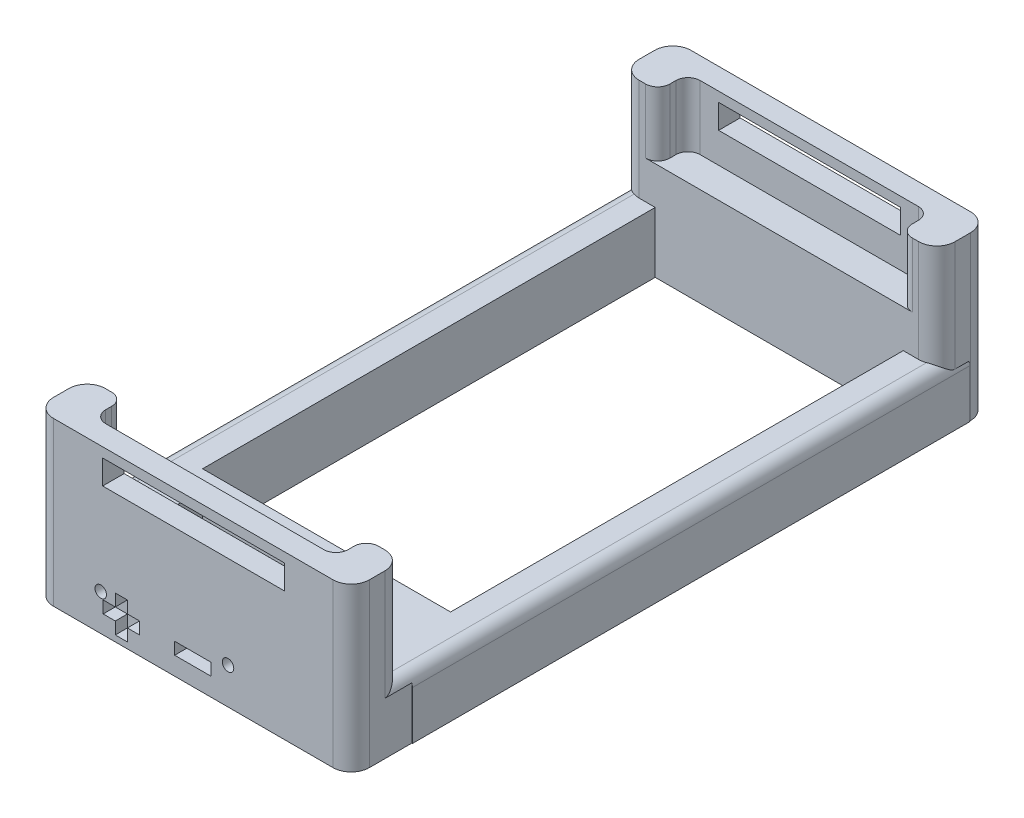
SolidWorks part; units mm, degrees
ref_plane "前视基准面" through (0, 0, 0) normal (0, 0, 1) x (1, 0, 0)
ref_plane "上视基准面" through (0, 0, 0) normal (0, 1, 0) x (1, 0, 0)
ref_plane "右视基准面" through (0, 0, 0) normal (1, 0, 0) x (0, 0, -1)
sketch "草图1" plane through (0, 0, 0) normal (0, 0, 1) x (1, 0, 0)
  line L0 (0, 0) -> (0, 15.5175) construction
  line L1 (32.43, -6) -> (-19.7, -6)
  line L3 (32.43, 10.25) -> (-19.7, 10.25)
  line L4 (-19.7, -6) -> (-19.7, 10.25)
  line L5 (32.43, 10.25) -> (32.43, -6)
  circle A0 centre (-10.5, 0) radius 0.95
  circle A1 centre (10.5, 0) radius 0.95
  point P0 (0, 0)
  dimension "D2" = 1.9
  dimension "D3" = 10.25
  dimension "D1" = 10.5
  dimension "D4" = 16.25
  dimension "D5" = 19.7
  dimension "D6" = 32.43
extrude "凸台-拉伸1" add sketch "草图1" along normal blind 10
sketch "草图2" plane through (0, 0, 0) normal (0, 0, -1) x (-1, 0, 0)
  line L0 (19.7, 10.25) -> (19.7, -6) construction
  line L1 (12.6, 4) -> (19.7, 4)
  line L2 (12.6, 4) -> (12.6, -6)
  line L3 (12.6, -6) -> (19.7, -6)
  line L4 (19.7, 4) -> (19.7, -6)
  line L5 (-12.6, 4) -> (-19.7, 4)
  line L6 (-12.6, 4) -> (-12.6, -6)
  line L7 (-12.6, -6) -> (-19.7, -6)
  line L8 (-19.7, 4) -> (-19.7, -6)
  point P8 (19.7, 4)
  dimension "D2" = 10
  dimension "D3" = 25.2
  dimension "D4" = 12.6
  dimension "D5" = 4
extrude "凸台-拉伸2" add sketch "草图2" along normal blind 11.95
sketch "草图3" plane through (0, 10.25, 0) normal (0, 1, 0) x (1, 0, 0)
  line L3 (32.43, -10) -> (-19.7, -10)
  line L4 (32.43, -10) -> (-19.7, -10) construction
  line L5 (-19.7, -10) -> (-19.7, -1.45)
  line L9 (-19.7, -1.45) -> (-13.635, -1.45)
  line L10 (-13.635, -1.45) -> (-13.635, -6.45)
  line L11 (26.365, -6.45) -> (-13.635, -6.45)
  line L12 (6.365, -6.45) -> (6.365, -10) construction
  line L13 (26.365, -1.45) -> (26.365, -6.45)
  line L14 (32.43, -10) -> (32.43, -1.45)
  line L15 (32.43, -1.45) -> (26.365, -1.45)
  line L16 (-19.7, -10) -> (-19.7, 0) construction
  point P5 (6.365, -10)
  point P11 (6.365, -6.45)
  point P17 (6.365, -10)
  dimension "D1" = 20
  dimension "D2" = 3.55
  dimension "D3" = 5
extrude "凸台-拉伸3" add sketch "草图3" along normal blind 10.6
sketch "草图4" plane through (0, 0, 10) normal (0, 0, 1) x (1, 0, 0)
  line L1 (21.4152, 19.2473) -> (-8.5848, 19.2473)
  line L2 (21.4152, 19.2473) -> (21.4152, 15.2473)
  line L3 (21.4152, 15.2473) -> (-8.5848, 15.2473)
  line L4 (-8.5848, 19.2473) -> (-8.5848, 15.2473)
  dimension "D1" = 30
  dimension "D2" = 8.5848
  dimension "D3" = 4
  dimension "D4" = 15.2473
extrude "切除-拉伸1" cut sketch "草图4" against normal blind 11
sketch "草图6" plane through (0, 0, -11.95) normal (0, 0, -1) x (-1, 0, 0)
  line L1 (19.7, -6) -> (14.05, -6)
  line L2 (19.7, -6) -> (19.7, 4)
  line L3 (19.7, 4) -> (14.05, 4)
  line L4 (14.05, -6) -> (14.05, 4)
  line L5 (19.7, 4) -> (12.6, 4) construction
  line L6 (12.6, -6) -> (19.7, -6) construction
  point P4 (19.7, -6)
  dimension "D1" = 5.65
extrude "凸台-拉伸4" add sketch "草图6" along normal blind 80
ref_plane "基准面1" through (6.4152, 0, 0) normal (-1, 0, 0) x (0, 0, 1)
mirror "镜向1" about plane through (6.4152, 0, 0) normal (-1, 0, 0) of "凸台-拉伸2", "凸台-拉伸4"
ref_plane "基准面2" through (0, 0, -42.6) normal (0, 0, 1) x (1, 0, 0)
mirror "镜向2" about plane through (0, 0, -42.6) normal (0, 0, 1) of "凸台-拉伸1", "凸台-拉伸3", "切除-拉伸1"
sketch "草图7" plane through (0, 10.25, 0) normal (0, 1, 0) x (1, 0, 0)
  line L0 (32.43, 0) -> (-19.7, 0) construction
  line L1 (-19.7, 0) -> (32.43, 0)
  line L2 (-19.7, 0) -> (-19.7, -1.45)
  line L3 (-19.7, -1.45) -> (32.43, -1.45)
  line L4 (32.43, 0) -> (32.43, -1.45)
  line L5 (32.43, 86.65) -> (26.365, 86.65) construction
  line L6 (32.43, 86.65) -> (-19.7, 86.65)
  line L7 (32.43, 86.65) -> (32.43, 84.8)
  line L8 (32.43, 84.8) -> (-19.7, 84.8)
  line L9 (-19.7, 86.65) -> (-19.7, 84.8)
  line L10 (32.43, 95.2) -> (32.43, 86.65) construction
  line L11 (-19.7, 85.2) -> (-19.7, 0) construction
  line L12 (-19.7, 86.65) -> (-19.7, 85.2) construction
extrude "切除-拉伸2" cut sketch "草图7" against normal up to surface (6.25 mm away) and the other way blind 80 up to face at (-15.45, 4, -32.3833)
sketch "草图8" plane through (0, 4, 0) normal (0, 1, 0) x (1, 0, 0)
  line L0 (-6.8696, 11.95) -> (-6.8696, 0) construction
  line L1 (-6.8696, 11.95) -> (4.1869, 11.95)
  line L2 (-6.8696, 11.95) -> (-6.8696, 0)
  line L3 (-6.8696, 0) -> (4.1869, 0)
  line L4 (4.1869, 11.95) -> (4.1869, 0)
  line L5 (0.2304, 11.95) -> (-6.8696, 11.95) construction
extrude "切除-拉伸3" cut sketch "草图8" against normal through all
sketch "草图9" plane through (12.6, 0, 0) normal (-1, 0, 0) x (0, 0, 1)
  line L0 (-11.95, 4) -> (0, 4) construction
  line L1 (-11.95, 4) -> (-8.85, 4)
  line L2 (-11.95, 4) -> (-11.95, -6)
  line L3 (-11.95, -6) -> (-8.85, -6)
  line L4 (-8.85, 4) -> (-8.85, -6)
  line L5 (-11.95, -6) -> (-11.95, 4) construction
  line L6 (-11.95, -6) -> (0, -6) construction
  dimension "D1" = 3.1
extrude "凸台-拉伸5" add sketch "草图9" along normal up to surface (25.2 mm away) up to face at (-12.6, -1, -5.975)
sketch "草图10" plane through (0, 0, 0) normal (0, 0, -1) x (-1, 0, 0)
  line L0 (12.6, -6) -> (-12.6, -6) construction
  line L1 (-12.6, -6) -> (-10.6, -6)
  line L2 (-12.6, -6) -> (-12.6, -4)
  line L3 (-12.6, -4) -> (-10.6, -4)
  line L4 (-10.6, -6) -> (-10.6, -4)
  line L5 (12.6, 4) -> (12.6, -6) construction
  line L6 (12.6, -6) -> (10.6, -6)
  line L7 (12.6, -6) -> (12.6, -4)
  line L8 (12.6, -4) -> (10.6, -4)
  line L9 (10.6, -6) -> (10.6, -4)
  dimension "D1" = 2
  dimension "D2" = 2
extrude "凸台-拉伸6" add sketch "草图10" along normal up to surface (8.85 mm away) up to face at (0, -1, -8.85)
sketch "草图11" plane through (0, 4, 0) normal (0, 1, 0) x (1, 0, 0)
  line L0 (-14.05, 85.2) -> (26.8804, 85.2) construction
  line L1 (-14.05, 85.2) -> (26.8815, 85.2)
  line L2 (-14.05, 85.2) -> (-14.05, 86.65)
  line L3 (-14.05, 86.65) -> (26.8815, 86.65)
  line L4 (26.8815, 85.2) -> (26.8815, 86.65)
  line L5 (32.43, 86.65) -> (26.365, 86.65) construction
extrude "切除-拉伸4" cut sketch "草图11" against normal through all
sketch "草图12" plane through (0, 4, 0) normal (0, 1, 0) x (1, 0, 0)
  line L1 (19.7, 11.95) -> (25.4304, 11.95)
  line L2 (19.7, 11.95) -> (19.7, 0)
  line L3 (19.7, 0) -> (25.4304, 0)
  line L4 (25.4304, 11.95) -> (25.4304, 0)
extrude "凸台-拉伸7" add sketch "草图12" against normal up to surface (10 mm away) up to face at (0, -6, -4.425)
fillet "圆角1" radius 3 8 edges at (-19.7, 7.425, -95.2) (32.43, 7.425, -95.2) (-19.7, 7.425, 10) (32.43, 7.425, 10) (32.43, 12.425, 1.45) (-19.7, 12.425, 1.45) (-19.7, 12.425, -86.65) (32.43, 12.425, -86.65)
fillet "圆角2" radius 2 2 edges at (32.5304, 4, -45.975) (-19.7, 4, -42.6)
sketch "草图13" plane through (0, 0, 1.45) normal (0, 0, -1) x (-1, 0, 0)
  line L0 (12.6, 4) -> (-12.6, 4) construction
  circle A0 centre (0, 5.05) radius 1.05
  dimension "D1" = 2.1
extrude "切除-拉伸5" cut sketch "草图13" against normal through all
fillet "圆角3" radius 2 8 edges at (26.365, 15.55, 6.45) (26.365, 15.55, 1.45) (-13.635, 15.55, 6.45) (-13.635, 15.55, 1.45) (26.365, 15.55, -86.65) (-13.635, 15.55, -86.65) (-13.635, 15.55, -91.65) (26.365, 15.55, -91.65)
sketch "草图14" plane through (0, 0, 0) normal (0, 0, -1) x (-1, 0, 0)
  line L8 (10.6, -4) -> (12.6, -4)
  line L9 (12.6, -4) -> (12.6, 4)
  line L10 (12.6, 4) -> (-12.6, 4)
  line L11 (-12.6, 4) -> (-12.6, -4)
  line L12 (-12.6, -4) -> (-10.6, -4)
  line L13 (-10.6, -4) -> (-10.6, -6)
  line L14 (-10.6, -6) -> (10.6, -6)
  line L15 (10.6, -6) -> (10.6, -4)
  line L16 (10.6, -4) -> (12.6, -4)
  line L17 (12.6, -4) -> (12.6, 4)
  line L18 (12.6, 4) -> (-12.6, 4)
  line L19 (-12.6, 4) -> (-12.6, -4)
  line L20 (-12.6, -4) -> (-10.6, -4)
  line L21 (-10.6, -4) -> (-10.6, -6)
  line L22 (-10.6, -6) -> (10.6, -6)
  line L23 (10.6, -6) -> (10.6, -4)
  circle A0 centre (-10.5, 0) radius 0.95 construction
  circle A1 centre (-10.5, 0) radius 0.95
  circle A2 centre (10.5, 0) radius 0.95 construction
  circle A3 centre (10.5, 0) radius 0.95
  dimension "D1" = 0
extrude "凸台-拉伸8" add sketch "草图14" along normal blind 3.4
sketch "草图15" plane through (0, 4, 0) normal (0, 1, 0) x (1, 0, 0)
  line L0 (-12.6, 8.85) -> (-12.6, 3.4) construction
  line L1 (-12.6, 3.4) -> (12.6, 3.4) construction
  line L2 (-12.6, 8.85) -> (12.6, 8.85) construction
  line L3 (12.6, 8.85) -> (12.6, 3.4) construction
  line L4 (-12.6, 8.85) -> (-12.6, 3.4)
  line L5 (-12.6, 3.4) -> (12.6, 3.4)
  line L6 (-12.6, 8.85) -> (12.6, 8.85)
  line L7 (12.6, 8.85) -> (12.6, 3.4)
  line L9 (-11, 8.85) -> (14.2, 8.85)
  line L10 (-11, 8.85) -> (-11, 3.4)
  line L11 (-11, 3.4) -> (14.2, 3.4)
  line L12 (14.2, 8.85) -> (14.2, 3.4)
  line M5 (12.6, 3.4) -> (-12.6, 3.4)
  line M6 (-12.6, 3.4) -> (-12.6, 8.85)
  line M7 (-12.6, 8.85) -> (12.6, 8.85)
  line M8 (12.6, 8.85) -> (12.6, 3.4)
  dimension "D1" = 1.6
extrude "凸台-拉伸9" add sketch "草图15" against normal through all contours L6 L10 M5 M8 | L10 L5 M7 M6 | L12 L9 L11 M8 region at (-11.8, 4, -6.125) region at (0.8, 4, -6.125) region at (13.4, 4, -6.125)
extrude "切除-拉伸6" cut sketch "草图15<3>" against normal through all contours L6 L10 M5 M8 | L12 L9 L11 M8 region at (0.8, 4, -6.125) region at (13.4, 4, -6.125)
sketch "草图15<3>" plane through (0, 4, 0) normal (0, 1, 0) x (1, 0, 0) same geometry as "草图15"
sketch "草图16" plane through (0, -6, 0) normal (0, -1, 0) x (-1, 0, 0)
  line L0 (11, 8.85) -> (-14.2, 8.85) construction
  line L5 (11, 3.4) -> (9, 3.4)
  line L6 (11, 3.4) -> (11, 8.85)
  line L7 (11, 8.85) -> (9, 8.85)
  line L8 (9, 3.4) -> (9, 8.85)
  line L10 (-14.2, 3.4) -> (-12.2, 3.4)
  line L11 (-14.2, 3.4) -> (-14.2, 8.85)
  line L12 (-14.2, 8.85) -> (-12.2, 8.85)
  line L13 (-12.2, 3.4) -> (-12.2, 8.85)
  dimension "D1" = 2
extrude "凸台-拉伸10" add sketch "草图16" against normal blind 2
sketch "草图17" plane through (0, 0, 10) normal (0, 0, 1) x (1, 0, 0)
  circle A0 centre (10.5, 0) radius 0.95 construction
  circle A1 centre (0, 5.05) radius 1.05 construction
  circle A2 centre (10.5, 0) radius 0.95
  circle A3 centre (0, 5.05) radius 1.05
  circle A4 centre (-10.5, 0) radius 0.95 construction
  circle A5 centre (-10.5, 0) radius 0.95
  circle M6 centre (-10.5, 0) radius 0.95
  circle M11 centre (10.5, 0) radius 0.95
extrude "凸台-拉伸11" add sketch "草图17" against normal up to surface (13.4 mm away) contours M6 | M11 region at (10.5, 0, 10) region at (-10.5, 0, 10)
extrude "凸台-拉伸12" add sketch "草图17<4>" against normal up to surface (8.55 mm away) up to face at (4.987, 12.095, 1.45)
sketch "草图17<4>" plane through (0, 0, 10) normal (0, 0, 1) x (1, 0, 0) same geometry as "草图17"
sketch "草图18" plane through (0, 0, 10) normal (0, 0, 1) x (1, 0, 0)
  circle A0 centre (0, 5.05) radius 1.05 construction
  circle A1 centre (-10.5, 0) radius 0.95 construction
  circle A2 centre (10.5, 0) radius 0.95 construction
  circle A3 centre (0, 5.05) radius 1.05 construction
  circle A4 centre (-10.5, 0) radius 0.95 construction
  circle A5 centre (10.5, 0) radius 0.95 construction
  circle A6 centre (1.6, 5.05) radius 1.05
  circle A7 centre (-8.9, 0) radius 0.95
  circle A8 centre (12.1, 0) radius 0.95
  dimension "D2" = 1.6
  dimension "D1" = 2
extrude "切除-拉伸7" cut sketch "草图18" against normal up to surface (13.4 mm away) contours A8 | A7 region at (-8.9, 0, 10) region at (12.1, 0, 10)
sketch "草图19" plane through (0, 0, -86.65) normal (0, 0, 1) x (1, 0, 0)
  circle A0 centre (-10.5, 0) radius 0.95 construction
  circle A1 centre (10.5, 0) radius 0.95 construction
  circle A2 centre (-10.5, 0) radius 0.95
  circle A3 centre (10.5, 0) radius 0.95
extrude "凸台-拉伸13" add sketch "草图19" against normal through all
sketch "草图20" plane through (0, -6, 0) normal (0, -1, 0) x (1, 0, 0)
  line L0 (-8.5, 1) -> (-2.5, 1)
  line L1 (-5.5, 4) -> (-5.5, -2)
  line L2 (3.5, 1) -> (9.5, 1)
  point P5 (-5.5, 1)
  point P6 (-5.5, 1)
  dimension "D1" = 6
  dimension "D2" = 5.5
  dimension "D3" = 6
  dimension "D4" = 1
extrude "切除-拉伸-薄壁1" cut sketch "草图20" against normal blind 2 thin thin type mid plane wall 2
sketch "草图21" plane through (0, 0, 10) normal (0, 0, 1) x (1, 0, 0)
  line L0 (-8.5, -2) -> (-2.5, -2)
  line L1 (-5.5, 1) -> (-5.5, -5)
  line L2 (3.3, -2) -> (9.3, -2)
  point P6 (-5.5, -2)
  point P9 (-5.5, -2)
  dimension "D1" = 2
  dimension "D2" = 5.5
  dimension "D3" = 3.3
  dimension "D4" = 6
extrude "切除-拉伸-薄壁2" cut sketch "草图21" against normal blind 2 thin thin type mid plane wall 2
